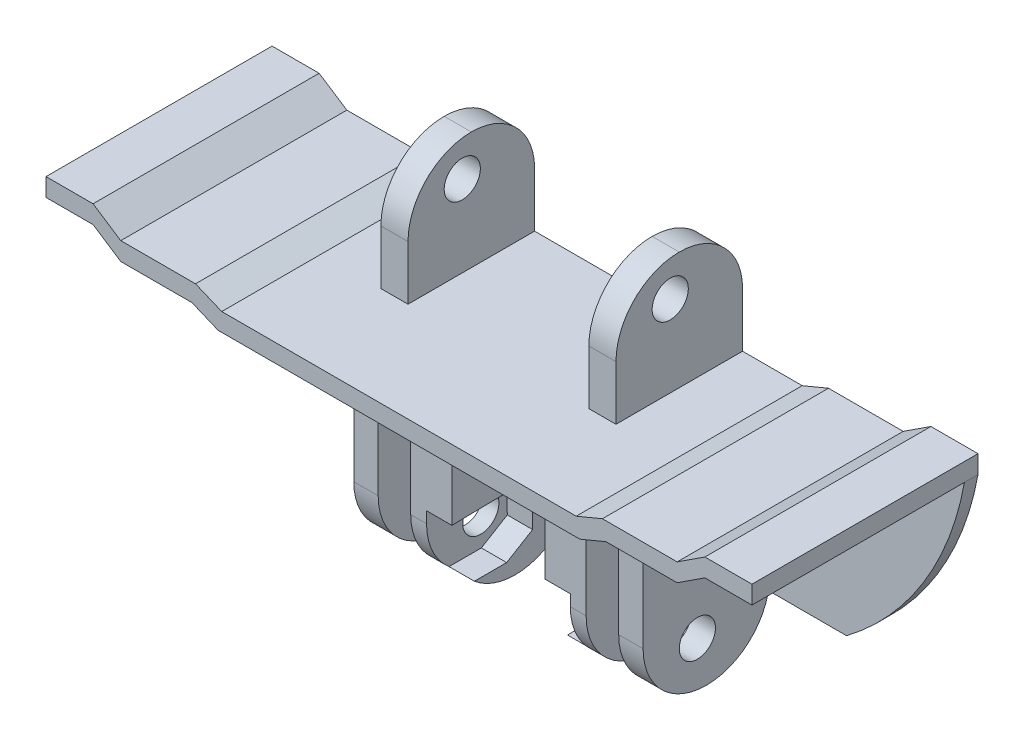
SolidWorks part; units mm, degrees
ref_plane "Front Plane" through (0, 0, 0) normal (0, 0, 1) x (1, 0, 0)
ref_plane "Top Plane" through (0, 0, 0) normal (0, 1, 0) x (1, 0, 0)
ref_plane "Right Plane" through (0, 0, 0) normal (1, 0, 0) x (0, 0, -1)
sketch "Sketch2" plane through (0, 0, 0) normal (0, 0, 1) x (1, 0, 0)
  line L0 (-5, 6) -> (-10, 6)
  line L1 (-5, 6) -> (5, 6) construction
  line L2 (-5, 6) -> (-5, -19) construction
  line L4 (5, 6) -> (5, -19) construction
  line L7 (-10, 6) -> (-10, -19)
  line L8 (-10, -19) -> (-5, -19)
  line L9 (-5, -19) -> (-5, 6)
  line L10 (0, 6) -> (0, -6) construction
  line L11 (10, -19) -> (5, -19)
  line L12 (10, 6) -> (10, -19)
  line L13 (5, 6) -> (10, 6)
  line L14 (5, -19) -> (5, 6)
  point P0 (0, 0)
  point P11 (0, 0)
  point P16 (0, 6)
  dimension "D1" = 25
  dimension "D2" = 10
  dimension "D3" = 5
extrude "Boss-Extrude1" add sketch "Sketch2" along normal blind 14
sketch "Sketch4" plane through (0, 0, 0) normal (0, 0, 1) x (1, 0, 0)
  line L0 (0, 0) -> (0, 50000) construction
  line L1 (-6.1796, 6) -> (49993.8204, 6) construction
  line L2 (-10, 6) -> (-20, 6)
  line L3 (10, 6) -> (20, 6)
  line L4 (-20, 6) -> (-22.9016, 7.2064)
  line L5 (-22.9016, 7.2064) -> (-26, 7.2064)
  line L6 (-10, 8) -> (-19.6008, 8)
  line L7 (-19.6008, 8) -> (-22.5024, 9.2064)
  line L8 (-22.5024, 9.2064) -> (-26, 9.2064)
  line L9 (-26, 9.2064) -> (-26, 7.2064)
  line L10 (-10, 6) -> (10, 6)
  line L11 (-10, 8) -> (10, 8)
  line L12 (10, 8) -> (19.6008, 8)
  line L13 (19.6008, 8) -> (22.5024, 9.2064)
  line L14 (20, 6) -> (22.9016, 7.2064)
  line L15 (22.9016, 7.2064) -> (26, 7.2064)
  line L17 (22.5024, 9.2064) -> (26, 9.2064)
  line L18 (-26, 7.2064) -> (-30.766, 7.2064)
  line L19 (-30.766, 7.2064) -> (-33.8312, 9.2064)
  line L20 (-33.8312, 9.2064) -> (-39.0379, 9.2064)
  line L21 (-39.0379, 9.2064) -> (-39.0379, 11.2064)
  line L22 (-39.0379, 11.2064) -> (-33.8312, 11.2064)
  line L23 (-26, 9.2064) -> (-30.766, 9.2064)
  line L24 (-30.766, 9.2064) -> (-33.8312, 11.2064)
  line L25 (26, 7.2064) -> (30.766, 7.2064)
  line L26 (26, 9.2064) -> (30.766, 9.2064)
  line L27 (30.766, 9.2064) -> (33.8312, 11.2064)
  line L28 (30.766, 7.2064) -> (33.8312, 9.2064)
  line L29 (33.8312, 9.2064) -> (39.0379, 9.2064)
  line L30 (39.0379, 9.2064) -> (39.0379, 11.2064)
  line L31 (39.0379, 11.2064) -> (33.8312, 11.2064)
  line L32 (26, 7.2064) -> (26, 9.2064)
  point P19 (0, 6)
  point P20 (0, 8)
  dimension "D1" = 10
  dimension "D2" = 2
extrude "Boss-Extrude3" add sketch "Sketch4" along normal blind 25 contours L23 L24 L22 L21 L20 L19 L18 L9 | L15 L32 L17 L13 L12 L11 L6 L7 L8 L9 L5 L4 L2 L10 L3 L14 | L32 L25 L28 L29 L30 L31 L27 L26 region at (0, 7.2239, 0) region at (-32.5189, 9.2402, 0) region at (32.5189, 9.2402, 0)
sketch "Sketch9" plane through (0, 0, 14) normal (0, 0, 1) x (1, 0, 0)
  line L0 (-10, -19) -> (-5, -19) construction
  line L1 (-5, 6) -> (-7.5, 6)
  line L2 (-5, 6) -> (-5, -19)
  line L3 (-5, -19) -> (-7.5, -19)
  line L4 (-7.5, 6) -> (-7.5, -19)
  line L5 (0, 7.972) -> (0, -7.972) construction
  line L6 (5, -19) -> (7.5, -19)
  line L7 (7.5, 6) -> (7.5, -19)
  line L8 (5, 6) -> (7.5, 6)
  line L9 (5, 6) -> (5, -19)
  point P11 (0, 0)
  dimension "D1" = 2.5
extrude "Cut-Extrude1" [suppressed] cut sketch "Sketch9" against normal blind 10
sketch "Sketch5" plane through (0, 0, 0) normal (0, 0, 1) x (1, 0, 0)
  line L0 (-10, 4.6) -> (-10, 50004.6) construction
  line L1 (0, 0) -> (0, 50000) construction
  line L2 (-10, 8) -> (-10, 21)
  line L3 (-19.6008, 8) -> (19.6008, 8) construction
  line L4 (-10, 21) -> (-13, 21)
  line L5 (-13, 21) -> (-13, 8)
  line L6 (-13, 8) -> (-10, 8)
  line L7 (13, 8) -> (10, 8)
  line L8 (13, 21) -> (13, 8)
  line L9 (10, 21) -> (13, 21)
  line L10 (10, 8) -> (10, 21)
  dimension "D1" = 3
  dimension "D2" = 13
extrude "Boss-Extrude4" add sketch "Sketch5" along normal blind 14
sketch "Sketch7" plane through (0, 0, 0) normal (0, 0, 1) x (1, 0, 0)
  line L0 (-13, 5.6) -> (-13, -49994.4) construction
  line L1 (-19.6008, 5.6) -> (-19.6008, -49994.4) construction
  line L2 (-10.0004, -19) -> (49989.9996, -19) construction
  line L3 (-15.0004, 6) -> (-50015.0004, 6) construction
  line L4 (-16, 6) -> (-16, -19)
  line L5 (-16, -19) -> (-13, -19)
  line L6 (-13, -19) -> (-13, 6)
  line L7 (-13, 6) -> (-16, 6)
  line L8 (0, 0) -> (0, -50000) construction
  line L13 (0, -13.75) -> (0, 13.75) construction
  line L14 (13, -19) -> (13, 6)
  line L15 (16, -19) -> (13, -19)
  line L16 (16, 6) -> (16, -19)
  line L17 (13, 6) -> (16, 6)
  dimension "D1" = 3
extrude "Boss-Extrude5" add sketch "Sketch7" along normal blind 14
sketch "Sketch15" plane through (0, -19, 0) normal (0, -1, 0) x (1, 0, 0)
  line L16 (-10, 14) -> (-9.7, 14)
  line L17 (-10, 14) -> (-5, 14) construction
  line L18 (-10, 14) -> (-10, 0) construction
  line L19 (-9.7, 14) -> (-9.7, 0)
  line L20 (-10, 0) -> (-5, 0) construction
  line L21 (-9.7, 0) -> (-10, 0)
  line L22 (-10, 0) -> (-10, 14)
  line L23 (0, -13.75) -> (0, 13.75) construction
  line L24 (9.7, 0) -> (10, 0)
  line L25 (9.7, 14) -> (9.7, 0)
  line L26 (10, 14) -> (9.7, 14)
  line L27 (10, 0) -> (10, 14)
  line L28 (-13, 14) -> (-13.3, 14)
  line L29 (-16, 14) -> (-13, 14) construction
  line L30 (-13.3, 14) -> (-13.3, 0)
  line L31 (-16, 0) -> (-13, 0) construction
  line L32 (-13.3, 0) -> (-13, 0)
  line L33 (-13, 0) -> (-13, 14)
  line L34 (13.3, 0) -> (13, 0)
  line L35 (13.3, 14) -> (13.3, 0)
  line L36 (13, 14) -> (13.3, 14)
  line L37 (13, 0) -> (13, 14)
  dimension "D1" = 0.3
  dimension "D2" = 0.3
extrude "Cut-Extrude2" cut sketch "Sketch15" against normal up to surface (25 mm away) up to face at (0, 6, 8.1)
sketch "Sketch16" plane through (0, -19, 0) normal (0, -1, 0) x (1, 0, 0)
  line L0 (-5, 14) -> (-5.15, 14)
  line L1 (-9.7, 14) -> (-5, 14) construction
  line L2 (-5.15, 14) -> (-5.15, 0)
  line L3 (-9.7, 0) -> (-5, 0) construction
  line L4 (-5.15, 0) -> (-5, 0)
  line L5 (-5, 0) -> (-5, 14)
  line L6 (0, -13.75) -> (0, 13.75) construction
  line L7 (5.15, 0) -> (5, 0)
  line L8 (5.15, 14) -> (5.15, 0)
  line L9 (5, 14) -> (5.15, 14)
  line L10 (5, 0) -> (5, 14)
  dimension "D1" = 0.15
extrude "Cut-Extrude3" cut sketch "Sketch16" against normal up to surface (25 mm away) up to face at (0, 6, 8.1)
fillet "Fillet1" radius 7 8 edges at (7.425, -19, 0) (7.425, -19, 14) (-7.425, -19, 0) (-7.425, -19, 14) (-14.65, -19, 0) (-14.65, -19, 14) (14.65, -19, 0) (14.65, -19, 14)
hole_wizard "Ø4.0mm Dowel Hole2" positions "Sketch10" profile "Sketch11" hole size "Ø4.0" standard "ANSI Metric" end condition through all
sketch "Sketch10" plane through (16, 0, 0) normal (1, 0, 0) x (0, 0, -1)
  line L7 (-25, 6) -> (0, 6) construction
  line L9 (-14, -12) -> (-14, 6) construction
  point P0 (-8, -14)
  dimension "D1" = 6
  dimension "D2" = 20
sketch "Sketch11" plane through (16, -14, 8) normal (0, 1, 0) x (0, 0, -1)
  line L0 (0, 0) -> (0, 55.0379)
  line L1 (0, 55.0379) -> (2, 55.0379)
  line L2 (2, 55.0379) -> (2, 0)
  line L5 (2, 0) -> (0, 0)
  line L11 (0, -6.35) -> (0, 107.95) construction
  dimension "Thru Hole Dia." = 4
  dimension "Thru Hole Depth" = 55.0379
fillet "Fillet2" radius 7 4 edges at (-11.5, 21, 0) (-11.5, 21, 14) (11.5, 21, 0) (11.5, 21, 14)
hole_wizard "Ø4.0mm Dowel Hole1" positions "Sketch12" profile "Sketch13" hole size "Ø4.0" standard "ANSI Metric"
sketch "Sketch12" plane through (13, 0, 0) normal (1, 0, 0) x (0, 0, -1)
  line L1 (-25, 8) -> (0, 8) construction
  line L2 (-25, 8) -> (0, 8)
  circle A8 centre (-8, -14) radius 2 construction
  circle A9 centre (-8, -14) radius 2
  point P10 (-8, 17)
  dimension "D1" = 9
sketch "Sketch13" plane through (13, 17, 8) normal (0, 1, 0) x (0, 0, -1)
  line L0 (0, 0) -> (0, 27.2017)
  line L1 (0, 27.2017) -> (2, 26)
  line L2 (2, 26) -> (2, 0)
  line L5 (2, 0) -> (0, 0)
  line L10 (0, 27.2017) -> (-2, 26) construction
  line L11 (0, -6.35) -> (0, 107.95) construction
  dimension "Hole Dia." = 4
  dimension "Hole Depth" = 26
  dimension "Drill Angle" = 118
sketch "Sketch14" plane through (0, 0, 0) normal (0, 0, 1) x (1, 0, 0)
  line L4 (0, 14.6739) -> (0, -14.6739) construction
  line L5 (-26, 7.2064) -> (-22.9016, 7.2064)
  line L6 (-26, 6) -> (-26, 7.2064)
  line L7 (-20, 6) -> (-26, 6)
  line L8 (-22.9016, 7.2064) -> (-20, 6)
  line L13 (-16, 6) -> (-20, 6)
  line L14 (-26, -12) -> (-26, 6)
  line L15 (-16, -12) -> (-26, -12)
  line L18 (-16, 6) -> (-16, -12)
  line L21 (16, 6) -> (16, -12)
  line L22 (16, -12) -> (26, -12)
  line L23 (26, -12) -> (26, 6)
  line L24 (16, 6) -> (20, 6)
  line L25 (22.9016, 7.2064) -> (20, 6)
  line L26 (20, 6) -> (26, 6)
  line L27 (26, 6) -> (26, 7.2064)
  line L28 (26, 7.2064) -> (22.9016, 7.2064)
  line L29 (33.8312, 9.2064) -> (39.0379, 9.2064) construction
  line L30 (30.766, 7.2064) -> (33.8312, 9.2064) construction
  line L31 (22.9016, 7.2064) -> (30.766, 7.2064) construction
  line L32 (33.8312, 9.2064) -> (39.0379, 9.2064)
  line L33 (30.766, 7.2064) -> (33.8312, 9.2064)
  line L34 (22.9016, 7.2064) -> (30.766, 7.2064)
  line L35 (-33.8312, 9.2064) -> (-39.0379, 9.2064) construction
  line L36 (-30.766, 7.2064) -> (-33.8312, 9.2064) construction
  line L37 (-22.9016, 7.2064) -> (-30.766, 7.2064) construction
  line L38 (-33.8312, 9.2064) -> (-39.0379, 9.2064)
  line L39 (-30.766, 7.2064) -> (-33.8312, 9.2064)
  line L40 (-22.9016, 7.2064) -> (-30.766, 7.2064)
  line L41 (-13.3, -12) -> (-16, -12) construction
  arc A0 (-39.0379, 9.2064) -> (-26, -12) centre (-5.4018, 15.2751) ccw
  arc A1 (26, -12) -> (39.0379, 9.2064) centre (5.4018, 15.2751) ccw
  point P11 (0, 0)
extrude "Boss-Extrude6" add sketch "Sketch14" along normal blind 1.5 contours L8 L5 L6 L7 | L14 L13 L7 | L27 L28 L25 L26 | L26 L24 L21 L22 L23 | L38 A0 L14 L6 L40 L39 | L23 A1 L32 L33 L34 L27 region at (-23.6483, 6.5391, 0) region at (-31.1404, 0.7095, 0) region at (-21, -3, 0) region at (21, -3, 0) region at (23.6483, 6.5391, 0) region at (31.1404, 0.7095, 0)
sketch "Sketch18" plane through (-5.15, 0, 0) normal (1, 0, 0) x (0, 0, -1)
  line L10 (-7.9408, -17.3481) -> (-22.2123, -17.3481)
  line L17 (-5.13, -12.2747) -> (-8.0592, -10.6519)
  line L18 (-8.0592, -10.6519) -> (-10.9291, -12.3772)
  line L19 (-10.9291, -12.3772) -> (-10.87, -15.7253)
  line L20 (-10.87, -15.7253) -> (-7.9408, -17.3481)
  line L21 (-7.9408, -17.3481) -> (-5.0709, -15.6228)
  line L22 (-5.0709, -15.6228) -> (-5.13, -12.2747)
  line L23 (-8.0592, -10.6519) -> (-22.2123, -10.902)
  line L24 (-22.2123, -10.902) -> (-22.2123, -17.3481)
  circle A0 centre (-8, -14) radius 2.9 construction
  circle M7 centre (-8, -14) radius 2
  arc M8 (-14, -12) -> (-7, -19) centre (-7, -12) ccw
  line M12 (-14, 6) -> (-14, -12)
  dimension "D1" = 5.8
extrude "Cut-Extrude4" cut sketch "Sketch18" against normal blind 2.8 contours L21 L22 L17 L18 L19 L20 M7 | L23 L24 L10 M8 M12 | L18 L23 L10 L20 L19 M12 M8 region at (-5.15, -13.6598, 11.722) region at (-5.15, -16.4589, 9.3623) region at (-5.15, -14.2277, 17.7524)
mirror "Mirror1" about plane through (0, 0, 0) normal (1, 0, 0) of "Cut-Extrude4"
ref_plane "Plane1" through (0, 0, 0) normal (1, 0, 0) x (0, 0, -1)
